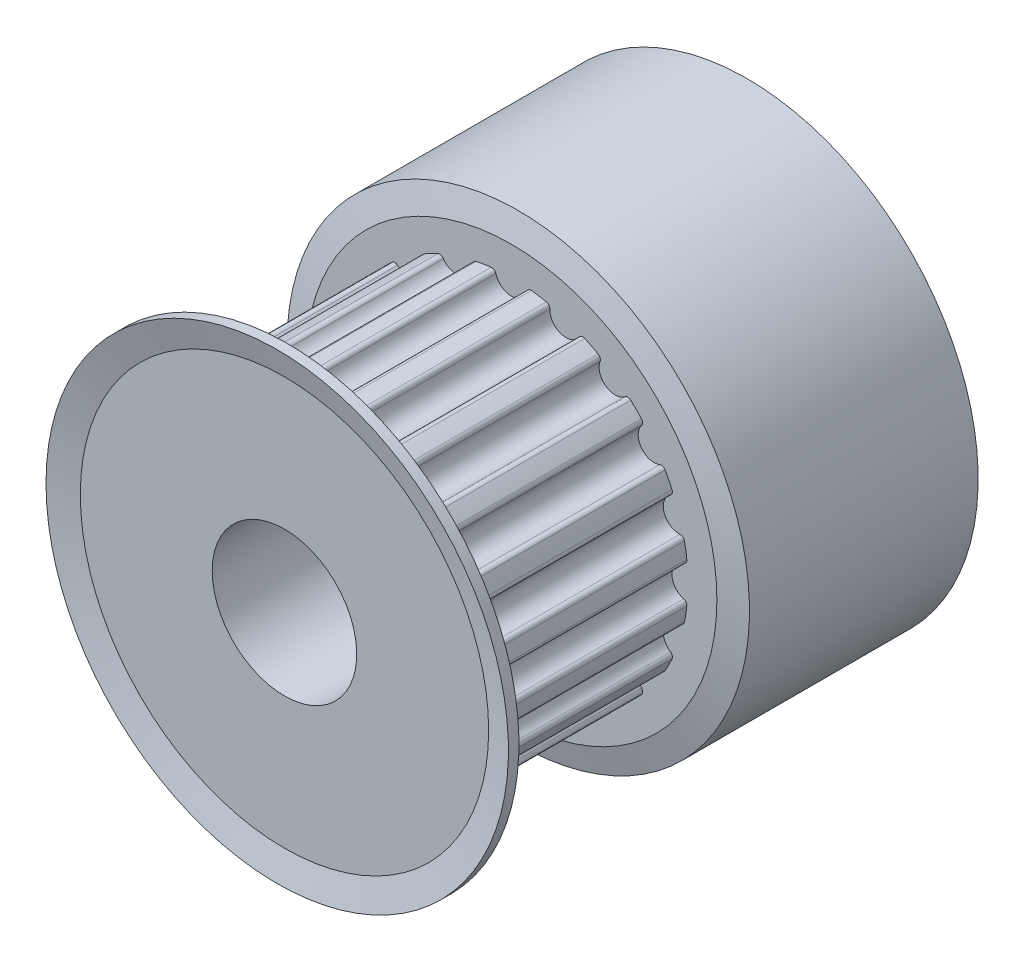
SolidWorks part; units mm, degrees
material "2024-T4"
ref_plane "Front Plane" through (0, 0, 0) normal (0, 0, 1) x (1, 0, 0)
ref_plane "Top Plane" through (0, 0, 0) normal (0, 1, 0) x (1, 0, 0)
ref_plane "Right Plane" through (0, 0, 0) normal (1, 0, 0) x (0, 0, -1)
sketch "Sketch1" plane through (0, 0, 0) normal (1, 0, 0) x (0, 0, -1)
  line L0 (0, 0) -> (-16, 0) construction
  line L1 (-16, 0) -> (-16, -2.5) construction
  line L2 (-16, -2.5) -> (0, -2.5) construction
  line L3 (0, -2.5) -> (0, 0) construction
  line L4 (0, -2.5) -> (0, -8)
  line L5 (0, -8) -> (-7.9115, -8)
  line L6 (-8.15, -7.11) -> (-8.15, -6.11)
  line L7 (-8.15, -6.11) -> (-15.65, -6.11)
  line L8 (-16, -2.5) -> (-16, -6.11)
  line L9 (-15.65, -6.11) -> (-15.65, -7.11)
  line L10 (-15.65, -7.11) -> (-15.8885, -8)
  line L11 (-16, -6.11) -> (-16, -7.0639)
  line L12 (-16, -7.0639) -> (-16.2508, -8)
  line L13 (-15.8885, -8) -> (-16.2508, -8)
  line L14 (-16, -7.0639) -> (-16.2265, -7.9094) construction
  line L15 (-11.9, -6.11) -> (-11.9, -9.189) construction
  line L16 (-8.15, -7.11) -> (-7.9115, -8)
  line L17 (-16, -2.5) -> (0, -2.5)
  dimension "D1" = 16
  dimension "D2" = 2.5
  dimension "D3" = 8
  dimension "D4" = 8.15
  dimension "D5" = 6.11
  dimension "D6" = 1
  dimension "D7" = 15
  dimension "D8" = 0.35
  dimension "D9" = 0.35
revolve "Revolve1" add sketch "Sketch1" angle 360 about L0 region at (0, -4.8998, 7.2518)
sketch "Sketch2" plane through (0, 0, 8.15) normal (0, 0, 1) x (1, 0, 0)
  circle A0 centre (0, 0) radius 6.11 construction
  circle A1 centre (0, 0) radius 6.11 construction
  circle A2 centre (0, 6.11) radius 0.555
  circle A3 centre (1.8881, 5.811) radius 0.555
  circle A4 centre (3.5914, 4.9431) radius 0.555
  circle A5 centre (4.9431, 3.5914) radius 0.555
  circle A6 centre (5.811, 1.8881) radius 0.555
  circle A7 centre (6.11, 0) radius 0.555
  circle A8 centre (5.811, -1.8881) radius 0.555
  circle A9 centre (4.9431, -3.5914) radius 0.555
  circle A10 centre (3.5914, -4.9431) radius 0.555
  circle A11 centre (1.8881, -5.811) radius 0.555
  circle A12 centre (0, -6.11) radius 0.555
  circle A13 centre (-1.8881, -5.811) radius 0.555
  circle A14 centre (-3.5914, -4.9431) radius 0.555
  circle A15 centre (-4.9431, -3.5914) radius 0.555
  circle A16 centre (-5.811, -1.8881) radius 0.555
  circle A17 centre (-6.11, 0) radius 0.555
  circle A18 centre (-5.811, 1.8881) radius 0.555
  circle A19 centre (-4.9431, 3.5914) radius 0.555
  circle A20 centre (-3.5914, 4.9431) radius 0.555
  circle A21 centre (-1.8881, 5.811) radius 0.555
  point P45 (0, 0)
  dimension "D1" = 1.11
  dimension "D2" = 20
extrude "Cut-Extrude1" cut sketch "Sketch2" along normal blind 7.5
fillet "Fillet1" radius 0.15 40 edges at (5.9583, 1.353, 11.9) (6.0848, 0.5544, 11.9) (6.0848, -0.5544, 11.9) (5.9583, -1.353, 11.9) (5.6157, -2.4076, 11.9) (5.2486, -3.128, 11.9) (4.5968, -4.0251, 11.9) (4.0251, -4.5968, 11.9) (3.128, -5.2486, 11.9) (2.4076, -5.6157, 11.9) (1.353, -5.9583, 11.9) (0.5544, -6.0848, 11.9) (-0.5544, -6.0848, 11.9) (5.6157, 2.4076, 11.9) (5.2486, 3.128, 11.9) (4.5968, 4.0251, 11.9) (4.0251, 4.5968, 11.9) (3.128, 5.2486, 11.9) (2.4076, 5.6157, 11.9) (1.353, 5.9583, 11.9) (0.5544, 6.0848, 11.9) (-0.5544, 6.0848, 11.9) (-1.353, 5.9583, 11.9) (-2.4076, 5.6157, 11.9) (-3.128, 5.2486, 11.9) (-1.353, -5.9583, 11.9) (-2.4076, -5.6157, 11.9) (-3.128, -5.2486, 11.9) (-4.0251, -4.5968, 11.9) (-4.5968, -4.0251, 11.9) (-5.2486, -3.128, 11.9) (-5.6157, -2.4076, 11.9) (-5.9583, -1.353, 11.9) (-6.0848, -0.5544, 11.9) (-6.0848, 0.5544, 11.9) (-5.9583, 1.353, 11.9) (-5.2486, 3.128, 11.9) (-5.6157, 2.4076, 11.9) (-4.0251, 4.5968, 11.9) (-4.5968, 4.0251, 11.9)
